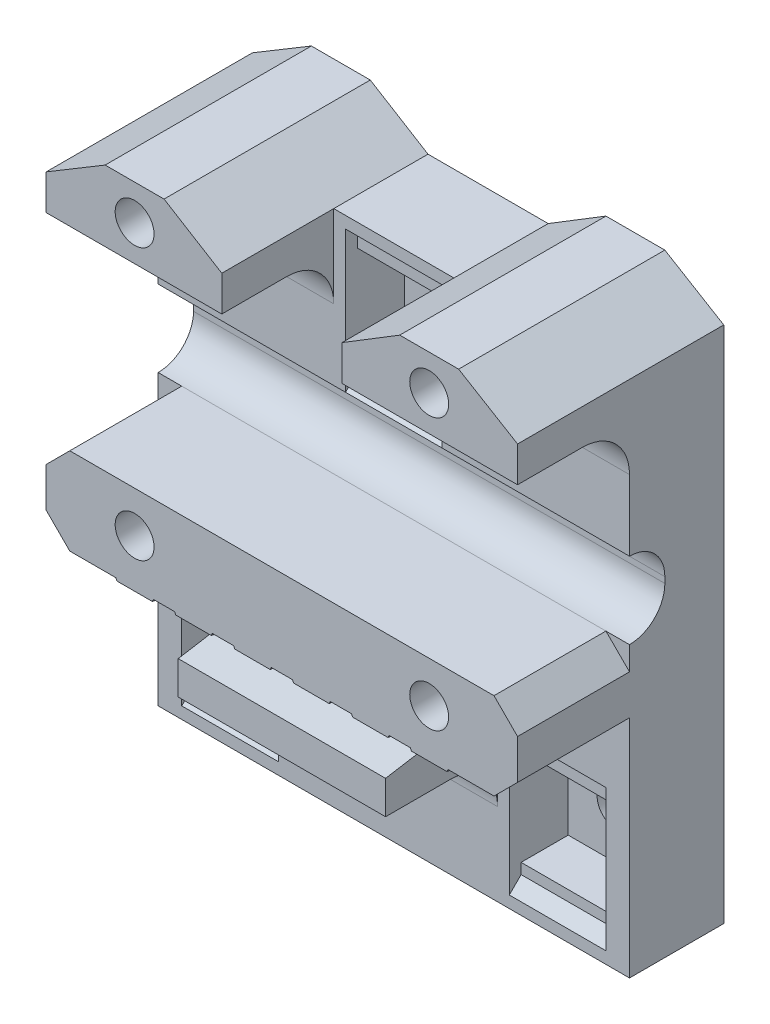
SolidWorks part; units mm, degrees
material "ABS"
ref_plane "Front Plane" through (0, 0, 0) normal (0, 0, 1) x (1, 0, 0)
ref_plane "Top Plane" through (0, 0, 0) normal (0, 1, 0) x (1, 0, 0)
ref_plane "Right Plane" through (0, 0, 0) normal (1, 0, 0) x (0, 0, -1)
sketch "Sketch1" plane through (0, 0, 0) normal (0, 0, 1) x (1, 0, 0)
  line L1 (-23.7591, 22) -> (52.715, 22) construction
  line L2 (0, -6) -> (0, 38)
  line L3 (0, 38) -> (40, 38)
  line L4 (40, -6) -> (40, 38)
  line L6 (0, -6) -> (40, -6)
  point P2 (0, 22)
  point P9 (40, 22)
  point P10 (0, 22)
  point P13 (40, 22)
  dimension "D1" = 44
  dimension "D2" = 40
extrude "Boss-Extrude1" add sketch "Sketch1" along normal blind 8
sketch "Sketch2" plane through (0, 0, 8) normal (0, 0, 1) x (1, 0, 0)
  line L0 (20, 38) -> (20, 20.7808) construction
  line L1 (15.9, 36) -> (24.1, 36)
  line L2 (15.9, 36) -> (15.9, 26)
  line L3 (15.9, 26) -> (24.1, 26)
  line L4 (24.1, 36) -> (24.1, 26)
  line L5 (40, 38) -> (0, 38) construction
  line L7 (40, 38) -> (0, 38) construction
  line L9 (2, 6) -> (10.2, 6)
  line L10 (2, 6) -> (2, -4)
  line L11 (2, -4) -> (10.2, -4)
  line L12 (10.2, 6) -> (10.2, -4)
  line L14 (29.8, 6) -> (29.8, -4)
  line L15 (38, -4) -> (29.8, -4)
  line L16 (38, 6) -> (38, -4)
  line L17 (38, 6) -> (29.8, 6)
  line L18 (15.9, 31) -> (24.1, 31) construction
  line L19 (2, 1) -> (38, 1) construction
  dimension "D1" = 8.2
  dimension "D2" = 10
  dimension "D3" = 2
  dimension "D4" = 4.1
  dimension "D5" = 30
  dimension "D6" = 2
extrude "Cut-Extrude1" cut sketch "Sketch2" against normal blind 1
sketch "Sketch3" plane through (0, 0, 7) normal (0, 0, 1) x (1, 0, 0)
  line L0 (15.9, 36) -> (15.9, 26) construction
  line L1 (15.9, 35.1) -> (24.1, 35.1)
  line L2 (15.9, 35.1) -> (15.9, 26.9)
  line L3 (15.9, 26.9) -> (24.1, 26.9)
  line L4 (24.1, 35.1) -> (24.1, 26.9)
  line L5 (24.1, 26) -> (24.1, 36) construction
  line L6 (24.1, 36) -> (15.9, 36) construction
  line L7 (15.9, 26) -> (24.1, 26) construction
  line L8 (2, 6) -> (2, -4) construction
  line L9 (2, 5.1) -> (10.2, 5.1)
  line L10 (2, 5.1) -> (2, -3.1)
  line L11 (2, -3.1) -> (10.2, -3.1)
  line L12 (10.2, 5.1) -> (10.2, -3.1)
  line L13 (10.2, -4) -> (10.2, 6) construction
  line L14 (29.8, 6) -> (29.8, -4) construction
  line L15 (29.8, 5.1) -> (38, 5.1)
  line L16 (29.8, 5.1) -> (29.8, -3.1)
  line L17 (29.8, -3.1) -> (38, -3.1)
  line L18 (38, 5.1) -> (38, -3.1)
  line L19 (38, -4) -> (38, 6) construction
  line L20 (2, -4) -> (10.2, -4) construction
  dimension "D1" = 0.9
  dimension "D2" = 0.9
  dimension "D3" = 0.9
extrude "Cut-Extrude2" cut sketch "Sketch3" against normal blind 4
chamfer "Chamfer1" distance 1 angle 45 6 edges at (20, 26, 8) (20, 36, 8) (33.9, -4, 8) (33.9, 6, 8) (6.1, -4, 8) (6.1, 6, 8)
sketch "Sketch4" plane through (0, 0, 3) normal (0, 0, 1) x (1, 0, 0)
  line L0 (24.1, 35.1) -> (15.9, 35.1) construction
  line L1 (15.9, 35.1) -> (15.9, 26.9) construction
  line L2 (2, 1) -> (38, 1) construction
  line L3 (2, 5.1) -> (2, -3.1) construction
  line L4 (38, -5) -> (38, 7) construction
  line L5 (6.1, 5.1) -> (6.1, -3.1) construction
  line L7 (2, -3.1) -> (10.2, -3.1) construction
  line L8 (33.9, 5.1) -> (33.9, -3.1) construction
  line L10 (29.8, -3.1) -> (38, -3.1) construction
  line L12 (10.2, 5.1) -> (2, 5.1) construction
  line L13 (38, 5.1) -> (29.8, 5.1) construction
  circle A0 centre (20, 31) radius 1.65
  circle A1 centre (6.1, 1) radius 1.65
  circle A2 centre (33.9, 1) radius 1.65
  dimension "D1" = 3.3
  dimension "D2" = 4.1
  dimension "D3" = 4.1
extrude "Cut-Extrude3" cut sketch "Sketch4" against normal through all
ref_plane "Plane1" through (20, 0, 0) normal (1, 0, 0) x (0, 0, -1)
sketch "Sketch5" plane through (0, 0, 8) normal (0, 0, 1) x (1, 0, 0)
  line L0 (-5.9966, 16) -> (42.103, 16) construction
  line L1 (20.9, 11.125) -> (19.1, 11.125)
  line L2 (28.8, 8.325) -> (28.8, 5)
  line L3 (11.2, 8.325) -> (28.8, 8.325)
  line L4 (21.5, 9.925) -> (23.5, 9.925)
  line L5 (20.9, 11.125) -> (21.5, 9.925)
  line L6 (20, -9.075) -> (20, 9.075) construction
  line L7 (7.5, 41) -> (7.5, 36.7771) construction
  line L8 (-5.9966, 5) -> (42.103, 5) construction
  line L9 (20, 30.9752) -> (20, -3.4501) construction
  line L10 (23.5, 9.925) -> (24.1, 11.125)
  line L11 (25.9, 11.125) -> (24.1, 11.125)
  line L12 (26.5, 9.925) -> (28.5, 9.925)
  line L13 (25.9, 11.125) -> (26.5, 9.925)
  line L15 (28.5, 9.925) -> (29.1, 11.125)
  line L16 (30.9, 11.125) -> (29.1, 11.125)
  line L17 (31.5, 9.925) -> (33.5, 9.925)
  line L18 (30.9, 11.125) -> (31.5, 9.925)
  line L19 (34.1, 11.125) -> (35.9, 11.125)
  line L20 (33.5, 9.925) -> (34.1, 11.125)
  line L21 (20.9, 11.125) -> (25.9, 11.125) construction
  line L22 (19.1, 11.125) -> (14.1, 11.125) construction
  line L23 (6.5, 9.925) -> (5.9, 11.125)
  line L24 (5.9, 11.125) -> (4.1, 11.125)
  line L25 (28.8, 5) -> (11.2, 5)
  line L26 (29.8, 7) -> (29.8, -5) construction
  line L27 (9.1, 11.125) -> (8.5, 9.925)
  line L28 (8.5, 9.925) -> (6.5, 9.925)
  line L30 (11.5, 9.925) -> (10.9, 11.125)
  line L31 (10.9, 11.125) -> (9.1, 11.125)
  line L32 (14.1, 11.125) -> (13.5, 9.925)
  line L33 (13.5, 9.925) -> (11.5, 9.925)
  line L35 (16.5, 9.925) -> (15.9, 11.125)
  line L36 (15.9, 11.125) -> (14.1, 11.125)
  line L37 (19.1, 11.125) -> (18.5, 9.925)
  line L38 (18.5, 9.925) -> (16.5, 9.925)
  line L39 (35.9, 11.125) -> (40, 11.125)
  line L40 (40, -6) -> (40, 38) construction
  line L41 (40, 11.125) -> (40, 18.5)
  line L42 (40, 18.5) -> (0, 18.5)
  line L43 (0, 18.5) -> (0, 11.125)
  line L44 (-5.9966, 27) -> (42.103, 27) construction
  line L45 (-5.9966, 35) -> (42.103, 35) construction
  line L46 (0, 38) -> (0, -6) construction
  line L47 (0, 35) -> (14.9, 35)
  line L48 (0, 35) -> (0, 38)
  line L49 (5, 41) -> (10, 41)
  line L50 (14.9, 35) -> (14.9, 38)
  line L51 (0, 38) -> (5, 41)
  line L52 (14.9, 38) -> (10, 41)
  line L53 (40, 38) -> (0, 38) construction
  line L54 (25.1, 38) -> (30, 41)
  line L55 (40, 38) -> (35, 41)
  line L56 (25.1, 35) -> (25.1, 38)
  line L57 (35, 41) -> (30, 41)
  line L58 (40, 35) -> (40, 38)
  line L59 (40, 35) -> (25.1, 35)
  line L61 (0, 11.125) -> (4.1, 11.125)
  line L62 (11.2, 8.325) -> (11.2, 5)
  line L63 (24.1, 11.125) -> (25.9, 11.125) [skipped]
  line L64 (29.1, 11.125) -> (30.9, 11.125) [skipped]
  circle A0 centre (20, 31) radius 1.65 construction
  point P53 (20, 11.125)
  point P83 (20, 5)
  point P84 (20, 8.325)
  dimension "D1" = 15
  dimension "D2" = 0.6
  dimension "D3" = 0.6
  dimension "D4" = 2
  dimension "D5" = 4.875
  dimension "D7" = 0.9
  dimension "D9" = 1
  dimension "D10" = 1.2
  dimension "D11" = 2.8
  dimension "D14" = 5
  dimension "D15" = 5.1
  dimension "D16" = 12.5
  dimension "D17" = 10
  dimension "D18" = 5
  dimension "D19" = 2.5
  dimension "D6" = 11
  dimension "D12" = 11
  dimension "D13" = 8
  dimension "D8" = 3
extrude "Boss-Extrude2" add sketch "Sketch5" along normal blind 9.5 and the other way up to surface (8 mm away) other way up to face at (35.55, 1, 0)
fillet "Fillet1" radius 4 3 edges at (32.55, 35, 8) (7.45, 35, 8) (20, 5, 8) tangent propagation no
sketch "Sketch6" plane through (0, 0, 17.5) normal (0, 0, 1) x (1, 0, 0)
  line L0 (7.5, 41) -> (7.5, 12.6708) construction
  line L1 (10, 41) -> (5, 41) construction
  line L2 (20, 31) -> (20, 13.7163) construction
  line L3 (20, -9.075) -> (20, 9.075) construction
  circle A0 centre (7.5, 38) radius 1.65
  circle A1 centre (7.5, 15) radius 1.65
  circle A2 centre (32.5, 38) radius 1.65
  circle A3 centre (32.5, 15) radius 1.65
  dimension "D1" = 3.3
  dimension "D2" = 23
  dimension "D3" = 3
extrude "Cut-Extrude4" cut sketch "Sketch6" against normal through all
chamfer "Chamfer2" distance 2 angle 45 4 edges at (40, 18.5, 12.75) (0, 18.5, 12.75) (40, 11.125, 12.75) (0, 11.125, 12.75)
sketch "Sketch7" plane through (0, 0, 8) normal (0, 0, 1) x (1, 0, 0)
  line L0 (0, 31) -> (0, 16.5) construction
  line L1 (0, 25) -> (40, 25)
  line L2 (0, 25) -> (0, 18.5)
  line L3 (0, 18.5) -> (40, 18.5)
  line L4 (40, 25) -> (40, 18.5)
  line L5 (40, 16.5) -> (40, 31) construction
  line L6 (24.1, 25) -> (15.9, 25) construction
  line L7 (38, 18.5) -> (2, 18.5) construction
extrude "Cut-Extrude5" cut sketch "Sketch7" against normal blind 3
fillet "Fillet2" radius 3 2 edges at (20, 18.5, 5) (20, 25, 5)
chamfer "Chamfer3" distance 3 distance2 1 6 edges at (7.5, 9.925, 17.5) (12.5, 9.925, 17.5) (17.5, 9.925, 17.5) (22.5, 9.925, 17.5) (27.5, 9.925, 17.5) (32.5, 9.925, 17.5) first distance on face at (7.5, 9.925, 12.75) first distance on face at (12.5, 9.925, 12.75) first distance on face at (17.5, 9.925, 12.75) first distance on face at (22.5, 9.925, 12.75) first distance on face at (27.5, 9.925, 12.75) first distance on face at (32.5, 9.925, 12.75)
chamfer "Chamfer4" distance 3 distance2 0.5 1 edges at (20, 8.325, 17.5) first distance on face at (20, 8.325, 12.75)
